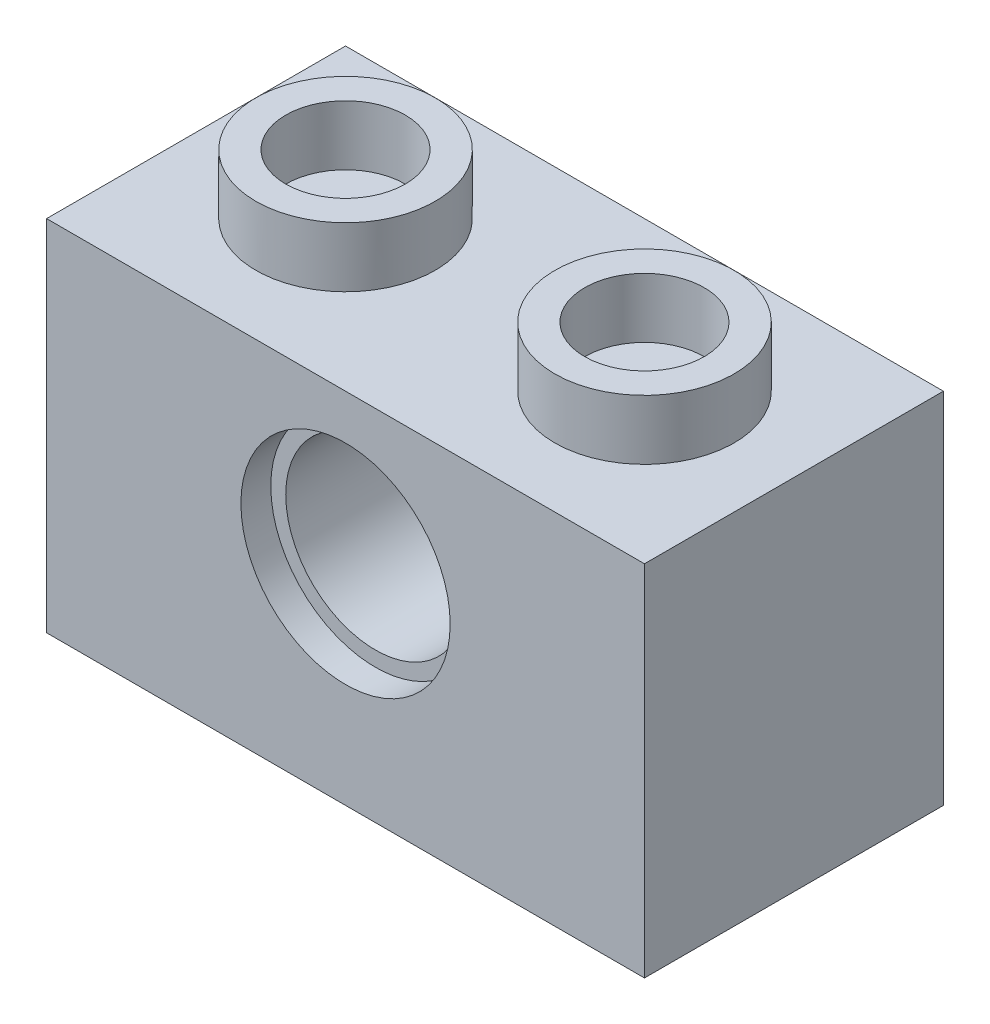
SolidWorks part; units mm, degrees
ref_plane "Front Plane" through (0, 0, 0) normal (0, 0, 1) x (1, 0, 0)
ref_plane "Top Plane" through (0, 0, 0) normal (0, 1, 0) x (1, 0, 0)
ref_plane "Right Plane" through (0, 0, 0) normal (1, 0, 0) x (0, 0, -1)
sketch "Sketch1" plane through (0, 0, 0) normal (0, 1, 0) x (1, 0, 0)
  line L1 (0, 0) -> (10, 0)
  line L2 (0, 0) -> (0, 5)
  line L3 (0, 5) -> (10, 5)
  line L4 (10, 0) -> (10, 5)
  line L5 (1, 4) -> (9, 4)
  line L6 (1, 4) -> (1, 1)
  line L7 (1, 1) -> (9, 1)
  line L8 (9, 4) -> (9, 1)
  point P9 (5, 4)
  point P10 (5, 5)
  point P11 (1, 2.5)
  point P12 (0, 2.5)
  dimension "D1" = 10
  dimension "D2" = 5
  dimension "D3" = 1
  dimension "D4" = 1
extrude "Boss-Extrude1" add sketch "Sketch1" along normal blind 6
sketch "Sketch2" plane through (1, 0, 0) normal (1, 0, 0) x (0, 0, -1)
  line L0 (1, 6) -> (1, 0) construction
  line L1 (4, 6) -> (1, 6)
  line L2 (4, 6) -> (4, 5)
  line L3 (4, 5) -> (1, 5)
  line L4 (1, 6) -> (1, 5)
  dimension "D1" = 1
extrude "Boss-Extrude2" add sketch "Sketch2" along normal up to next
sketch "Sketch4" plane through (0, 6, 0) normal (0, 1, 0) x (1, 0, 0)
  line L0 (0, 5) -> (0, 0) construction
  line L1 (0, 2.5) -> (10, 2.5)
  line L2 (10, 0) -> (10, 5) construction
  line L3 (5, 5) -> (5, 0)
  line L4 (10, 5) -> (0, 5) construction
  line L5 (0, 0) -> (10, 0) construction
  circle A0 centre (2.5, 2.5) radius 1.5
  circle A1 centre (7.5, 2.5) radius 1.5
  circle A2 centre (7.5, 2.5) radius 1
  circle A3 centre (2.5, 2.5) radius 1
  dimension "D2" = 3
  dimension "D3" = 2
  dimension "D1" = 2.5
extrude "Boss-Extrude3" add sketch "Sketch4" along normal blind 1 contours L1 A0 | L1 A0 | A1 L1 | A1 L1 region at (2.5, 6, -3.5335) region at (3.75, 6, -2.4665) region at (7.5, 6, -3.9665) region at (6.25, 6, -2.4665)
sketch "Sketch6" plane through (0, 5, 0) normal (0, -1, 0) x (-1, 0, 0)
  line L0 (-1, 2.5) -> (-9, 2.5)
  line L1 (-1, 1) -> (-1, 4) construction
  line L2 (-9, 4) -> (-9, 1) construction
  circle A0 centre (-2.5, 2.5) radius 0.75
  circle A1 centre (-2.5, 2.5) radius 1.5
  circle A2 centre (-5, 2.5) radius 1
extrude "Boss-Extrude4" add sketch "Sketch6" along normal up to surface (5 mm away) contours L0 A2 | L0 A2 region at (5, 5, -2.0756) region at (5, 5, -2.9244) up to face at (5, 0, -2.5)
sketch "Sketch7" plane through (0, 0, -5) normal (0, 0, -1) x (-1, 0, 0)
  line L0 (-5, 0) -> (-5, 6)
  line L1 (-10, 0) -> (0, 0) construction
  line L2 (-10, 6) -> (0, 6) construction
  circle A0 centre (-5, 3.5) radius 1.5
  circle A1 centre (-5, 3.5) radius 1.75
  dimension "D1" = 3
  dimension "D3" = 3.5
  dimension "D2" = 2.5
extrude "Boss-Extrude5" add sketch "Sketch7" against normal up to surface (5 mm away) contours L0 A1 A0 | L0 A1 A0 | L0 A0 | L0 A0 region at (6.7109, 3.5, -5) region at (4.9609, 1.875, -5) region at (5.6366, 3.5, -5) region at (4.3634, 3.5, -5) up to face at (5, 3, 0)
extrude "Cut-Extrude2" cut sketch "Sketch7<3>" against normal up to surface (5 mm away) contours L0 A0 | L0 A0 region at (5.6366, 3.5, -5) region at (4.3634, 3.5, -5) up to face at (5, 3, 0)
sketch "Sketch7<3>" plane through (0, 0, -5) normal (0, 0, -1) x (-1, 0, 0) same geometry as "Sketch7"
extrude "Cut-Extrude3" cut sketch "Sketch7<4>" against normal blind 0.5 contours L0 A1 A0 | L0 A1 A0 region at (6.7109, 3.5, -5) region at (4.9609, 1.875, -5)
sketch "Sketch7<4>" plane through (0, 0, -5) normal (0, 0, -1) x (-1, 0, 0) same geometry as "Sketch7"
sketch "Sketch8" plane through (0, 0, 0) normal (0, 0, 1) x (1, 0, 0)
  circle A0 centre (5, 3.5) radius 1.75
  dimension "D1" = 3.5
extrude "Cut-Extrude4" cut sketch "Sketch8" against normal blind 0.5
